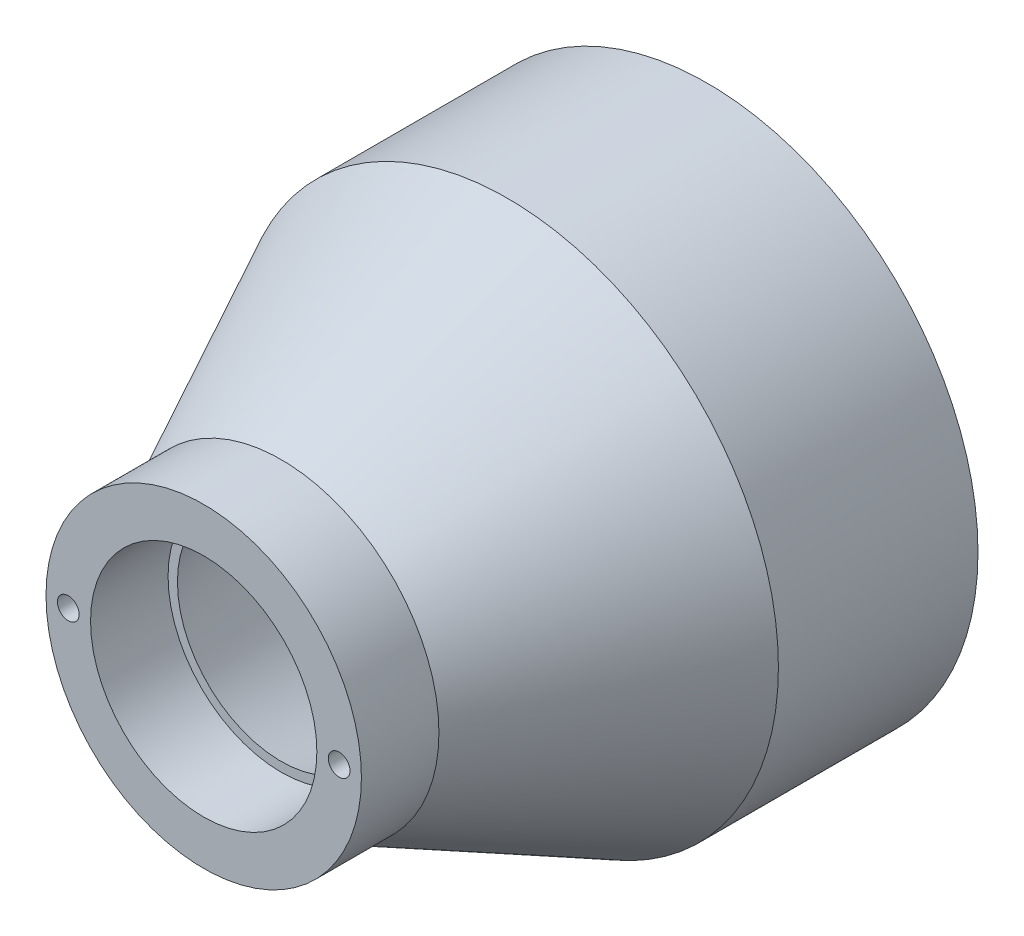
SolidWorks part; units mm, degrees
ref_plane "Plan de face" through (0, 0, 0) normal (0, 0, 1) x (1, 0, 0)
ref_plane "Plan de dessus" through (0, 0, 0) normal (0, 1, 0) x (1, 0, 0)
ref_plane "Plan de droite" through (0, 0, 0) normal (1, 0, 0) x (0, 0, -1)
sketch "Esquisse1" plane through (0, 0, 0) normal (0, 0, 1) x (1, 0, 0)
  circle A0 centre (0, 0) radius 12.7
  circle A1 centre (0, 0) radius 17.7
extrude "Boss.-Extru.1" add sketch "Esquisse1" along normal blind 8.7
sketch "Esquisse2" plane through (0, 0, 0) normal (0, 0, -1) x (-1, 0, 0)
  circle A0 centre (0, 0) radius 11.2
  circle A1 centre (0, 0) radius 30.4
extrude "Boss.-Extru.2" add sketch "Esquisse2" along normal blind 47.8
chamfer "Chanfrein1" distance 25.4 angle 26.565 1 edges at (-30.4, 0, 0) first distance on face at (-30.4, 0, -47.8)
chamfer "Chanfrein3" distance 49.8 angle 12.675 1 edges at (-11.2, 0, -47.8) first distance on face at (-11.2, 0, -47.8)
sketch "Esquisse3" [suppressed] plane through (0, 0, 7.7) normal (0, 0, 1) x (1, 0, 0)
  line L0 (-12.7, 0) -> (-17.7, 0)
  line L1 (12.7, 0) -> (17.7, 0)
  circle A0 centre (0, 0) radius 12.7 construction
  circle A1 centre (0, 0) radius 17.7 construction
  circle A2 centre (0, 0) radius 12.7 construction
other "PerçageAvancé1" [suppressed] parameters "D0"=0
sketch "Esquisse4" plane through (0, 0, 7.7) normal (0, 0, 1) x (1, 0, 0)
  line L0 (-12.7, 0) -> (-17.7, 0) construction
  line L1 (12.7, 0) -> (17.7, 0) construction
  point P0 (-15.2, 0)
  point P4 (15.2, 0)
sketch "Esquisse5" plane through (-15.2, 0, 7.7) normal (0, 1, 0) x (1, 0, 0)
  line L0 (0, 0) -> (0, 1.1176)
  line L1 (0, -0.5588) -> (0, 1.6764) construction
  line L2 (1.7856, 0) -> (1.7856, 1.1176)
  line L3 (0, 0) -> (1.7856, 0)
  line L4 (1.7856, 1.1176) -> (0, 1.1176)
  dimension "D1" = 1.1176
  dimension "D2" = 3.5712
sketch "Sketch1" plane through (0, 0, 8.7) normal (0, 0, 1) x (1, 0, 0)
  line L0 (-12.7, 0) -> (-17.7, 0)
  line L1 (-17.7, 0) -> (12.7, 0)
  line L2 (12.7, 0) -> (17.7, 0)
  circle A0 centre (0, 0) radius 12.7 construction
  circle A1 centre (0, 0) radius 12.7 construction
  circle A2 centre (0, 0) radius 17.7 construction
hole_wizard "#41 (0.096) Diameter Hole1" positions "Sketch2" profile "Sketch4" hole size "#41" standard "ANSI Inch"
sketch "Sketch2" plane through (0, 0, 8.7) normal (0, 0, 1) x (1, 0, 0)
  line L0 (-12.7, 0) -> (-17.7, 0) construction
  line L1 (12.7, 0) -> (17.7, 0) construction
  point P0 (-15.2, 0)
  point P4 (15.2, 0)
sketch "Sketch4" plane through (-15.2, 0, 8.7) normal (1, 0, 0) x (0, -1, 0)
  line L0 (0, 0) -> (0, 5.7326)
  line L1 (0, 5.7326) -> (1.2192, 5)
  line L2 (1.2192, 5) -> (1.2192, 0)
  line L5 (1.2192, 0) -> (0, 0)
  line L10 (0, 5.7326) -> (-1.2192, 5) construction
  line L11 (0, -6.35) -> (0, 107.95) construction
  dimension "Hole Dia." = 2.4384
  dimension "Hole Depth" = 5
  dimension "Drill Angle" = 118
